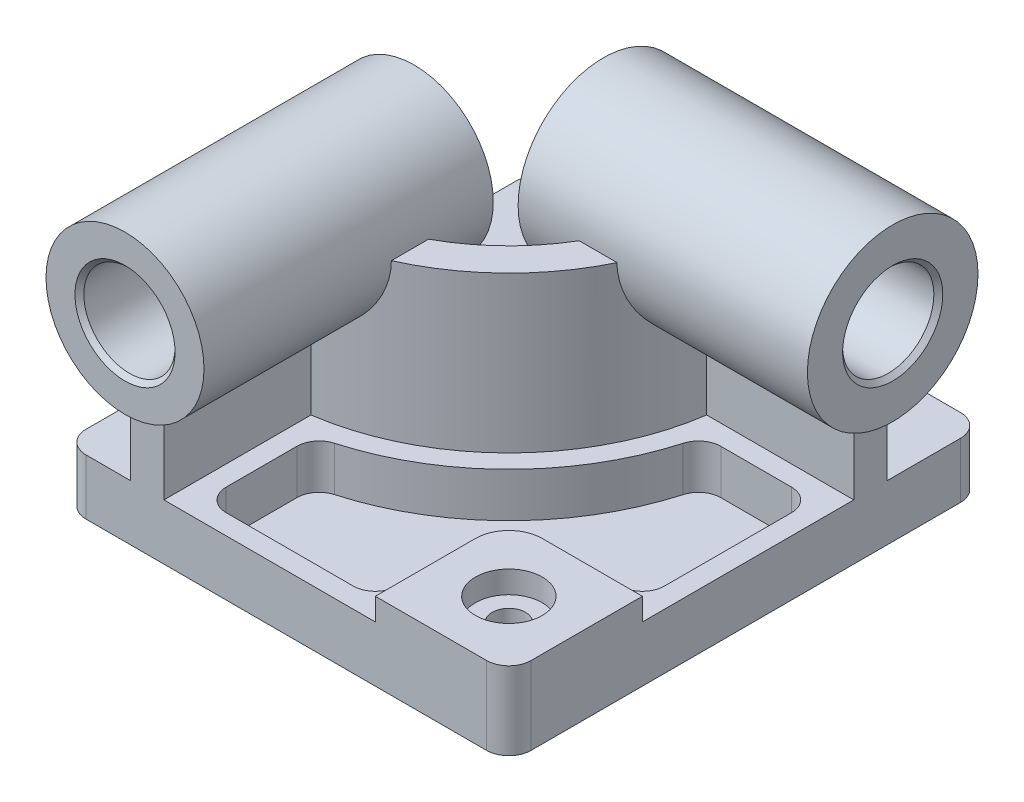
SolidWorks part; units mm, degrees
material "Alloy Steel"
ref_plane "Front Plane" through (0, 0, 0) normal (0, 0, 1) x (1, 0, 0)
ref_plane "Top Plane" through (0, 0, 0) normal (0, 1, 0) x (1, 0, 0)
ref_plane "Right Plane" through (0, 0, 0) normal (1, 0, 0) x (0, 0, -1)
sketch "Sketch1" plane through (0, 0, 0) normal (0, 1, 0) x (1, 0, 0)
  line L0 (-70, -106.5) -> (-70, -26.5)
  line L1 (90, 106.5) -> (-90, 106.5)
  line L2 (100, 96.5) -> (100, -96.5)
  line L3 (90, -106.5) -> (-90, -106.5)
  line L4 (-100, 96.5) -> (-100, -96.5)
  line L5 (100, 106.5) -> (-100, -106.5) construction
  line L6 (100, -106.5) -> (-100, 106.5) construction
  line L7 (90, -106.5) -> (40, -106.5)
  line L8 (100, -96.5) -> (100, -46.5)
  line L9 (100, -46.5) -> (55, -46.5)
  line L10 (40, -106.5) -> (40, -61.5)
  line L11 (20, 63.5) -> (100, 63.5)
  line L14 (-55, -106.5) -> (-55, -40.423)
  line L15 (33.923, 48.5) -> (100, 48.5)
  line L16 (-46, -87.5) -> (-46, -55.7476)
  line L17 (49.2476, 39.5) -> (81, 39.5)
  line L18 (21, -97.5) -> (-36, -97.5)
  line L19 (81, -37.5) -> (55, -37.5)
  line L20 (31, -87.5) -> (31, -61.5)
  line L21 (91, 29.5) -> (91, -27.5)
  line L22 (91, 96.5) -> (91, -96.5) construction
  line L23 (-46, -106.5) -> (-46, -47.9451) construction
  line L24 (90, -97.5) -> (-90, -97.5) construction
  line L25 (41.4451, 39.5) -> (100, 39.5) construction
  line L26 (100, -37.5) -> (55, -37.5) construction
  line L27 (31, -106.5) -> (31, -61.5) construction
  line L28 (-70, -106.5) -> (-55, -106.5)
  line L29 (100, 63.5) -> (100, 48.5)
  arc A0 (-70, -26.5) -> (20, 63.5) centre (-70, 63.5) ccw
  arc A1 (81, -37.5) -> (91, -27.5) centre (81, -27.5) ccw
  arc A2 (-55, -40.423) -> (33.923, 48.5) centre (-70, 63.5) ccw
  arc A3 (55, -46.5) -> (40, -61.5) centre (55, -61.5) ccw
  arc A4 (-90, -106.5) -> (-100, -96.5) centre (-90, -96.5) cw
  arc A5 (100, -96.5) -> (90, -106.5) centre (90, -96.5) cw
  arc A6 (90, 106.5) -> (100, 96.5) centre (90, 96.5) cw
  arc A7 (-90, 106.5) -> (-100, 96.5) centre (-90, 96.5) ccw
  arc A8 (-38.7419, -46.1309) -> (39.6309, 32.2419) centre (-70, 63.5) ccw
  arc A9 (55, -37.5) -> (31, -61.5) centre (55, -61.5) ccw
  arc A10 (91, 29.5) -> (81, 39.5) centre (81, 29.5) ccw
  arc A11 (-46, -47.9451) -> (41.4451, 39.5) centre (-70, 63.5) ccw construction
  arc A12 (39.6309, 32.2419) -> (49.2476, 39.5) centre (49.2476, 29.5) cw
  arc A13 (-46, -55.7476) -> (-38.7419, -46.1309) centre (-36, -55.7476) cw
  arc A14 (-36, -97.5) -> (-46, -87.5) centre (-36, -87.5) cw
  arc A15 (21, -97.5) -> (31, -87.5) centre (21, -87.5) ccw
  arc A16 (90, -106.5) -> (100, -96.5) centre (90, -96.5) ccw
  point P0 (0, 0)
  dimension "D4" = 80
  dimension "D8" = 15
  dimension "D9" = 10
  dimension "D6" = 10
  dimension "D11" = 10
  dimension "D1" = 213
  dimension "D2" = 200
  dimension "D3" = 60
  dimension "D5" = 170
  dimension "D7" = 15
  dimension "D10" = 9
extrude "Boss-Extrude1" add sketch "Sketch1" along normal blind 25 contours L1 A7 L4 A4 L3 L0 A0 L11 L2 A6 | L14 A2 L15 L2 L11 A0 L0 L3 | A3 L9 L2 L15 A2 L14 L3 L10 A15 L18 A14 L16 A13 A8 A12 L17 A10 L21 A1 L19 A9 L20 | L18 A15 L20 A9 L19 A1 L21 A10 L17 A12 A8 A13 L16 A14 | A5 L2 L9 A3 L10 L3 region at (-31.6903, 0, -39.0093) region at (-3.0976, 0, 3.4024) region at (-52.808, 0, 73.4615) region at (70.1957, 0, 76.6957) region at (26.8204, 0, 33.3204)
extrude "Boss-Extrude2" add sketch "Sketch1<3>" along normal blind 35 contours L10 A3 L9 L8 A16 L7
sketch "Sketch1<3>" plane through (0, 0, 0) normal (0, 1, 0) x (1, 0, 0) same geometry as "Sketch1"
extrude "Boss-Extrude3" add sketch "Sketch1<4>" along normal blind 95 contours L0 A0 L11 L29 L15 A2 L14 L28
sketch "Sketch1<4>" plane through (0, 0, 0) normal (0, 1, 0) x (1, 0, 0) same geometry as "Sketch1"
extrude "Cut-Extrude1" cut sketch "Sketch1<5>" against normal offset from surface (20 mm away) 5 from surface contours L18 A14 L16 A13 A8 A12 L17 A10 L21 A1 L19 A9 L20 A15 up to face at (0, 0, 0) starting at face at (-19.3431, 25, -18.0431)
sketch "Sketch1<5>" plane through (0, 0, 0) normal (0, 1, 0) x (1, 0, 0) same geometry as "Sketch1"
sketch "Sketch3" plane through (100, 0, 0) normal (1, 0, 0) x (0, 0, -1)
  line L0 (63.5, 95) -> (48.5, 95) construction
  circle A0 centre (56, 95) radius 38.3333
  dimension "D1" = 76.6667
extrude "Boss-Extrude4" add sketch "Sketch3" along normal blind 10 and the other way blind 120
sketch "Sketch4" plane through (0, 0, 106.5) normal (0, 0, 1) x (1, 0, 0)
  line L0 (-70, 95) -> (-55, 95) construction
  circle A0 centre (-62.5, 95) radius 35.5
  dimension "D1" = 71
extrude "Boss-Extrude5" add sketch "Sketch4" along normal blind 10 and the other way blind 120
sketch "Sketch5" plane through (110, 0, 0) normal (1, 0, 0) x (0, 0, -1)
  circle A0 centre (56, 95) radius 20.5
  circle A1 centre (56, 95) radius 38.3333 construction
  point P3 (0, 0)
  dimension "D1" = 41
extrude "Cut-Extrude2" cut sketch "Sketch5" against normal up to surface (130 mm away) up to face at (-20, 95, -94.3333)
sketch "Sketch6" plane through (0, 0, 116.5) normal (0, 0, 1) x (1, 0, 0)
  circle A0 centre (-62.5, 95) radius 20.5
  dimension "D1" = 41
extrude "Cut-Extrude3" cut sketch "Sketch6" against normal up to surface (130 mm away) up to face at (-27, 95, -13.5)
chamfer "Chamfer1" distance 2 angle 45 4 edges at (110, 95, -76.5) (-20, 95, -76.5) (-42, 95, 116.5) (-42, 95, -13.5)
sketch "Sketch7" plane through (0, 35, 0) normal (0, 1, 0) x (1, 0, 0)
  line L0 (100, -96.5) -> (100, -46.5) construction
  line L1 (55, -46.5) -> (100, -46.5) construction
  circle A0 centre (70, -76.5) radius 15
  circle A1 centre (70, -76.5) radius 7.5
  dimension "D1" = 30
  dimension "D3" = 30
  dimension "D4" = 15
  dimension "D2" = 30
extrude "Cut-Extrude4" cut sketch "Sketch7" against normal up to surface (35 mm away) contours A1 up to face at (0, 0, 0)
extrude "Cut-Extrude5" cut sketch "Sketch7<3>" against normal blind 10
sketch "Sketch7<3>" plane through (0, 35, 0) normal (0, 1, 0) x (1, 0, 0) same geometry as "Sketch7"
